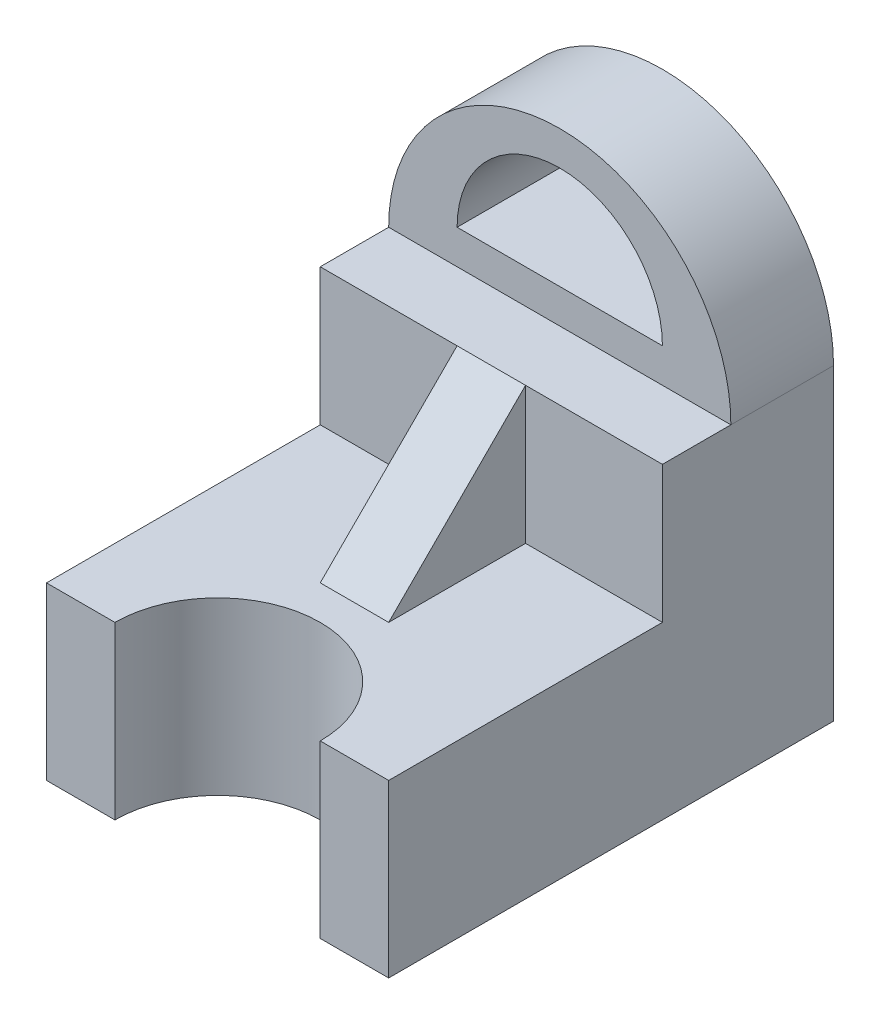
SolidWorks part; units mm, degrees
ref_plane "Front Plane" through (0, 0, 0) normal (0, 0, 1) x (1, 0, 0)
ref_plane "Top Plane" through (0, 0, 0) normal (0, 1, 0) x (1, 0, 0)
ref_plane "Right Plane" through (0, 0, 0) normal (1, 0, 0) x (0, 0, -1)
sketch "Sketch1" plane through (0, 0, 0) normal (0, 0, 1) x (1, 0, 0)
  line L0 (0, 0) -> (0, 28262.0592) construction
  line L1 (0, 0) -> (-28262.0592, 0) construction
  line L2 (27, 90) -> (-27, 90)
  line L3 (45, 0) -> (-45, 0)
  line L4 (45, 0) -> (45, 45)
  line L5 (45, 45) -> (-45, 45)
  line L6 (-45, 0) -> (-45, 45)
  line L7 (45, 45) -> (-45, 45)
  line L8 (45, 45) -> (45, 81)
  line L9 (45, 81) -> (-45, 81)
  line L10 (-45, 45) -> (-45, 81)
  arc A0 (-45, 81) -> (45, 81) centre (0, 81) cw
  arc A1 (-27, 90) -> (27, 90) centre (0, 90) cw
  point P15 (0, 90)
  dimension "D4" = 27
  dimension "D1" = 90
  dimension "D2" = 45
  dimension "D3" = 36
  dimension "D5" = 9
extrude "Boss-Extrude1" add sketch "Sketch1" along normal blind 117 contours L6 L3 L4 L5 region at (0, 22.5, 0)
extrude "Boss-Extrude2" add sketch "Sketch1<3>" along normal blind 45 contours L10 L5 L8 L9 region at (0, 63, 0)
sketch "Sketch1<3>" plane through (0, 0, 0) normal (0, 0, 1) x (1, 0, 0) same geometry as "Sketch1"
extrude "Boss-Extrude3" add sketch "Sketch1<4>" along normal blind 27 contours A0 L9 L2 A1 region at (0, 82.0062, 0)
sketch "Sketch1<4>" plane through (0, 0, 0) normal (0, 0, 1) x (1, 0, 0) same geometry as "Sketch1"
sketch "Sketch5" plane through (0, 45, 0) normal (0, 1, 0) x (1, 0, 0)
  line L0 (0, 0) -> (0, 50000) construction
  line L1 (45, 0) -> (-45, 0) construction
  line L2 (45, -117) -> (-45, -117) construction
  line L3 (-27, -117) -> (27, -117)
  arc A0 (-27, -117) -> (27, -117) centre (0, -117) cw
  point P4 (0, 0)
  point P8 (-17.5419, -117)
  dimension "D1" = 54
extrude "Cut-Extrude1" cut sketch "Sketch5" against normal up to next
sketch "Sketch7" plane through (0, 0, 0) normal (1, 0, 0) x (0, 0, -1)
  line L0 (-45, 81) -> (-81, 45)
  line L1 (-117, 45) -> (-45, 45) construction
  line L2 (-81, 45) -> (-45, 45)
  line L3 (-45, 45) -> (-45, 81)
extrude "Boss-Extrude4" add sketch "Sketch7" along normal mid plane 18
